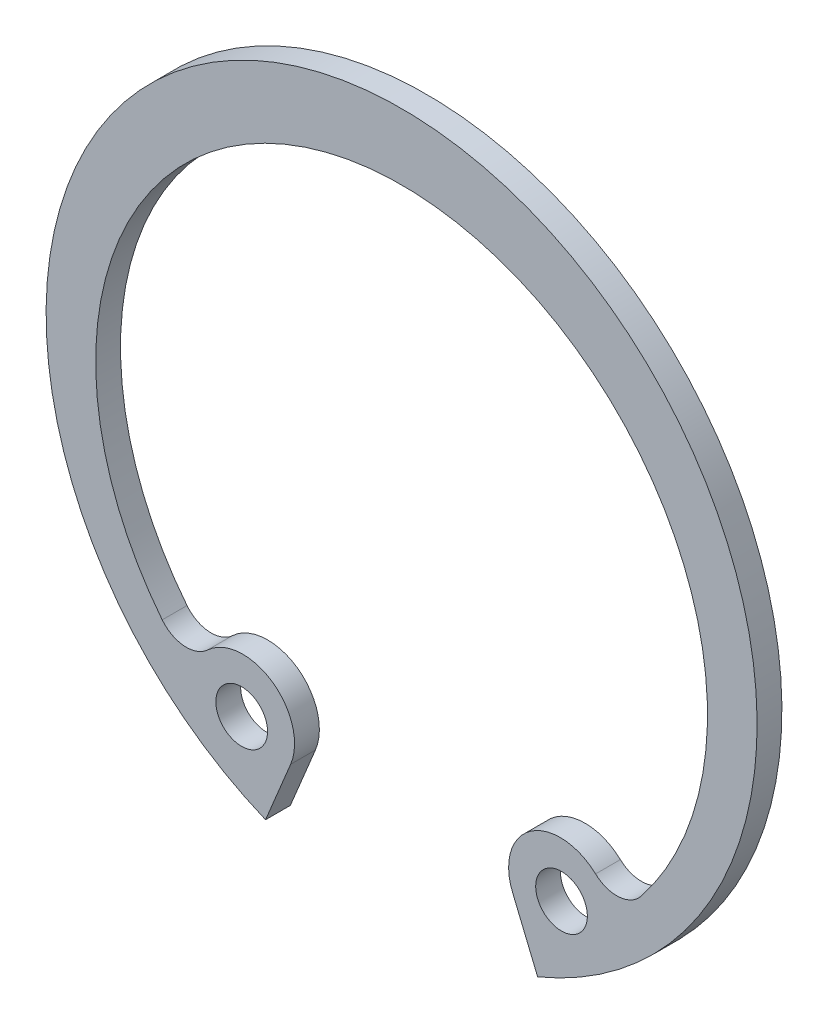
SolidWorks part; units mm, degrees
ref_plane "前视" through (0, 0, 0) normal (0, 0, 1) x (1, 0, 0)
ref_plane "上视" through (0, 0, 0) normal (0, 1, 0) x (1, 0, 0)
ref_plane "右视" through (0, 0, 0) normal (1, 0, 0) x (0, 0, -1)
sketch "尺寸草图" plane through (0, 0, 0) normal (0, 0, 1) x (1, 0, 0)
  line L0 (-17.2, 0) -> (17.2, 0) construction
  line L1 (0, 0) -> (-14.8956, -8.6) construction
  circle A0 centre (0, 0) radius 17.2
  point P5 (-12.4, 0)
  point P6 (12.9, 0)
  point P7 (2.5, 0)
  point P8 (14.4, 0)
  point P10 (-2.95, 0)
  point P11 (-0.8, 0)
  point P12 (-5.45, 0)
  point P13 (-13.6, 0)
  point P14 (24.0755, 13.9)
  dimension "DD" = 34.4
  dimension "d" = 29.6
  dimension "RR" = 14.4
  dimension "R1" = 2.5
  dimension "R2" = 1.5
  dimension "aa" = 45
  dimension "a" = 5.45
  dimension "d1" = 2.5
  dimension "c" = 0.8
  dimension "s" = 1.2
sketch "草图1" plane through (0, 0, 0) normal (0, 0, 1) x (1, 0, 0)
  line L0 (0, 17.2) -> (0, -15.8907) construction
  line L1 (-5.3687, -12.9611) -> (-6.5822, -15.8907)
  line L2 (-7.795, -12.2859) -> (-7.6784, -12.0044) construction
  line L3 (0, 0) -> (-6.5822, -15.8907) construction
  line L4 (5.3687, -12.9611) -> (6.5822, -15.8907)
  arc A0 (6.5822, -15.8907) -> (-6.5822, -15.8907) centre (0, 0) ccw
  arc A1 (11.5817, -10.0143) -> (-11.5817, -10.0143) centre (0, -0.8) ccw
  circle A2 centre (-7.7367, -12.1451) radius 1.25
  arc A3 (-5.3687, -12.9611) -> (-9.3843, -10.1769) centre (-7.6784, -12.0044) ccw
  arc A4 (-9.3843, -10.1769) -> (-11.5817, -10.0143) centre (-10.4079, -9.0804) cw
  circle A5 centre (7.7367, -12.1451) radius 1.25
  arc A6 (5.3687, -12.9611) -> (9.3843, -10.1769) centre (7.6784, -12.0044) cw
  arc A7 (9.3843, -10.1769) -> (11.5817, -10.0143) centre (10.4079, -9.0804) ccw
  dimension "D1" = 34.4
  dimension "D2" = 29.6
  dimension "D5" = 2.5
  dimension "D7" = 2.5
  dimension "D8" = 1.5
  dimension "D9" = 5.45
  dimension "D3" = 0.8
  dimension "D4" = 22.5
  dimension "D6" = 14.4
extrude "基体-拉伸" add sketch "草图1" along normal blind 0.6 and the other way blind 0.6
equation "\"D1@草图1\" = \"DD@尺寸草图\" "
equation "\"D2@草图1\"=\"d@尺寸草图\""
equation "\"D3@草图1\" = \"c@尺寸草图\""
equation "\"D6@草图1\" = \"RR@尺寸草图\""
equation "\"D8@草图1\" = \"R2@尺寸草图\""
equation "\"D7@草图1\" = \"R1@尺寸草图\""
equation "\"D4@草图1\" = \"aa@尺寸草图\"/2"
equation "\"D9@草图1\" = \"a@尺寸草图\""
equation "\"D5@草图1\" = \"d1@尺寸草图\""
equation "\"D1@基体-拉伸\" = \"s@尺寸草图\"/2"
equation "\"D2@基体-拉伸\" = \"D1@基体-拉伸\""
